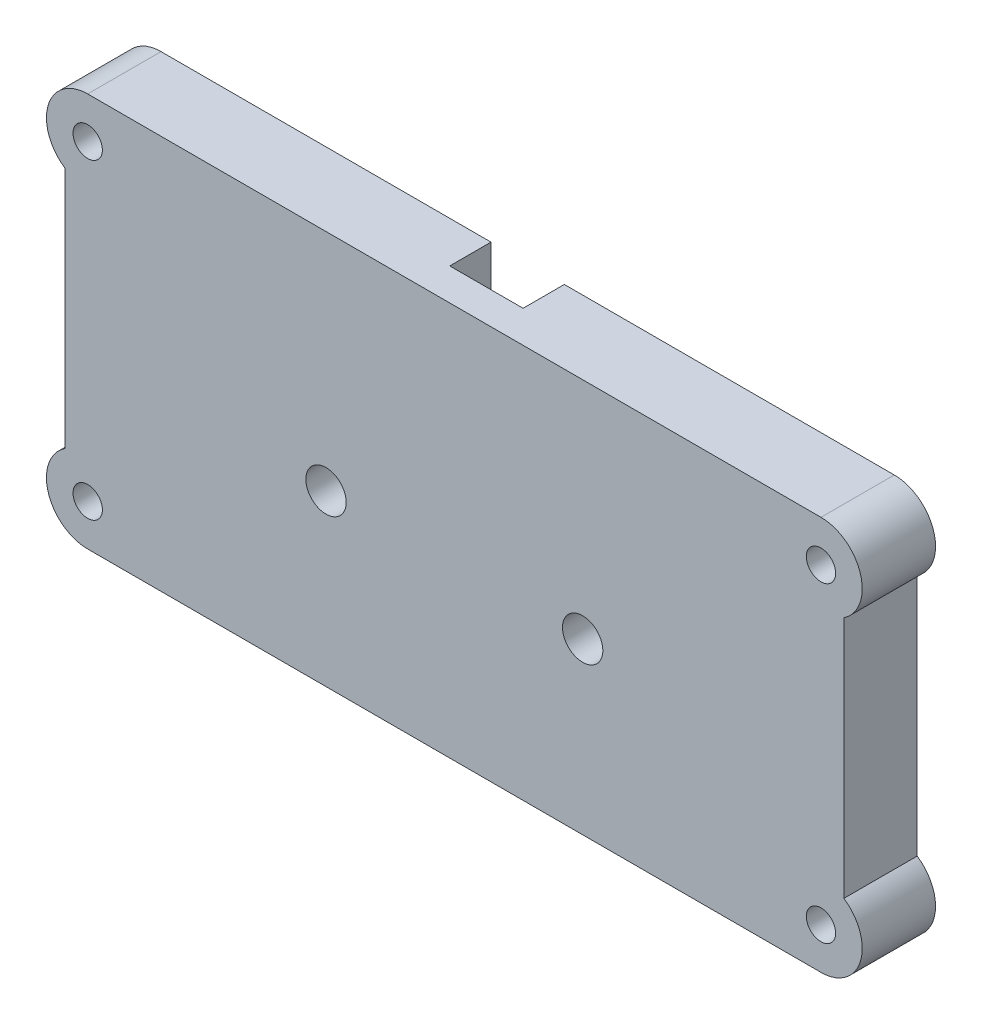
SolidWorks part; units mm, degrees
ref_plane "Front Plane" through (0, 0, 0) normal (0, 0, 1) x (1, 0, 0)
ref_plane "Top Plane" through (0, 0, 0) normal (0, 1, 0) x (1, 0, 0)
ref_plane "Right Plane" through (0, 0, 0) normal (1, 0, 0) x (0, 0, -1)
sketch "Sketch1" plane through (0, 0, 0) normal (0, 0, 1) x (1, 0, 0)
  line L0 (0, 62.8997) -> (0, -49.5687) construction
  line L5 (-81.1125, 0) -> (72.4755, 0) construction
  line L6 (-42.5, -13.2583) -> (-42.5, 13.2583)
  line L8 (0, 0) -> (-15.8735, 15.8735) construction
  line L10 (42.5, -13.2583) -> (42.5, 13.2583)
  line L11 (-40, 21.5) -> (40, 21.5)
  line L12 (-40, -21.5) -> (40, -21.5)
  line L13 (-5.4899, 9.874) -> (-9.8288, 14.2128)
  line L14 (-14.2128, 9.8288) -> (-9.874, 5.4899)
  line L15 (14.2128, 9.8288) -> (9.874, 5.4899)
  line L16 (5.4899, 9.874) -> (9.8288, 14.2128)
  line L17 (14.2128, -9.8288) -> (9.874, -5.4899)
  line L18 (5.4899, -9.874) -> (9.8288, -14.2128)
  line L19 (-5.4899, -9.874) -> (-9.8288, -14.2128)
  line L20 (-14.2128, -9.8288) -> (-9.874, -5.4899)
  line L22 (-7.1, -3.85) -> (7.1, -3.85)
  line L23 (-7.1, -3.85) -> (-7.1, 3.85)
  line L24 (-7.1, 3.85) -> (7.1, 3.85) construction
  line L25 (7.1, -3.85) -> (7.1, 3.85)
  line L26 (-7.1, -3.85) -> (7.1, 3.85) construction
  line L27 (-7.1, 3.85) -> (7.1, -3.85) construction
  line L28 (-7.1, 3.85) -> (7.1, 3.85) construction
  line L29 (-7.1, 3.85) -> (-7.1, 7.6)
  line L30 (-7.1, 7.6) -> (7.1, 7.6)
  line L31 (7.1, 3.85) -> (7.1, 7.6)
  line L32 (-4, 21.5) -> (4, 21.5)
  line L33 (-4, 21.5) -> (-4, 7.6)
  line L34 (-4, 7.6) -> (4, 7.6)
  line L35 (4, 21.5) -> (4, 7.6)
  arc A1 (-40, 21.5) -> (-42.5, 13.2583) centre (-40, 17) ccw
  arc A2 (-40, -21.5) -> (-42.5, -13.2583) centre (-40, -17) cw
  arc A3 (40, 21.5) -> (42.5, 13.2583) centre (40, 17) cw
  arc A4 (40, -21.5) -> (42.5, -13.2583) centre (40, -17) ccw
  circle A5 centre (0, 0) radius 17 construction
  arc A6 (-9.8288, 14.2128) -> (-14.2128, 9.8288) centre (-12.0208, 12.0208) ccw
  arc A7 (9.8288, 14.2128) -> (14.2128, 9.8288) centre (12.0208, 12.0208) cw
  arc A8 (-9.8288, -14.2128) -> (-14.2128, -9.8288) centre (-12.0208, -12.0208) cw
  arc A9 (9.8288, -14.2128) -> (14.2128, -9.8288) centre (12.0208, -12.0208) ccw
  arc A10 (-5.4899, 9.874) -> (5.4899, 9.874) centre (0, 15.364) ccw
  arc A11 (-5.4899, -9.874) -> (5.4899, -9.874) centre (0, -15.364) cw
  arc A12 (9.874, 5.4899) -> (9.874, -5.4899) centre (15.364, 0) ccw
  arc A13 (-9.874, 5.4899) -> (-9.874, -5.4899) centre (-15.364, 0) cw
  circle A14 centre (-40, 17) radius 1.6
  circle A15 centre (40, 17) radius 1.6
  circle A16 centre (-40, -17) radius 1.6
  circle A17 centre (40, -17) radius 1.6
  point P17 (-42.5, 0)
  point P23 (42.5, 0)
  dimension "D1" = 9
  dimension "D5" = 34
  dimension "D6" = 45
  dimension "D8" = 15.2
  dimension "D9" = 3.2
  dimension "D10" = 14.2
  dimension "D2" = 34
  dimension "D3" = 2.5
  dimension "D4" = 80
  dimension "D7" = 6.2
  dimension "D11" = 7.7
  dimension "D12" = 8
extrude "Boss-Extrude1" add sketch "Sketch1" along normal blind 8 contours L12 A4 L10 A3 L11 A1 L6 A2 A13 L14 A6 L13 A10 L16 A7 L15 A12 L17 A9 L18 A11 L19 A8 L20 | L22 L25 L24 L23 | L23 A13 L20 A8 L19 A11 L18 A9 L17 A12 L25 L22 | L14 A13 L23 L24 L25 A12 L15 A7 L16 A10 L13 A6 | L33 L32 L35 L34 region at (-41.5116, 0, 0) region at (-4.4277, 8.1549, 0) region at (0, 1.875, 0)
extrude "Cut-Extrude4" cut sketch "Sketch1<7>" along normal blind 1.7 contours L13 A6 L14 A13 L20 A8 L19 A11 L18 A9 L17 A12 L15 A7 L16 A10
sketch "Sketch1<7>" plane through (0, 0, 0) normal (0, 0, 1) x (1, 0, 0) same geometry as "Sketch1"
extrude "Cut-Extrude5" cut sketch "Sketch1<8>" along normal blind 7.4 contours L22 L25 L31 L30 L29 L23
sketch "Sketch1<8>" plane through (0, 0, 0) normal (0, 0, 1) x (1, 0, 0) same geometry as "Sketch1"
extrude "Cut-Extrude6" cut sketch "Sketch1<9>" along normal blind 4.5 contours L33 L34 L35 L32
sketch "Sketch1<9>" plane through (0, 0, 0) normal (0, 0, 1) x (1, 0, 0) same geometry as "Sketch1"
sketch "Sketch2" plane through (0, 0, 8) normal (0, 0, 1) x (1, 0, 0)
  line L0 (0, 9.8235) -> (0, -9.9073) construction
  line L1 (-20, 8) -> (20, 8) construction
  line L2 (-20, 8) -> (-20, -10) construction
  line L3 (-20, -10) -> (20, -10) construction
  line L4 (20, 8) -> (20, -10) construction
  line L5 (-21.3685, 0) -> (19.1836, 0) construction
  circle A0 centre (-14, -3) radius 2.2
  circle A1 centre (14, -3) radius 2.2
  circle A2 centre (0, -0.0419) radius 4 construction
  point P0 (0, 0)
  point P16 (0, 0)
  dimension "D3" = 4.4
  dimension "D4" = 28
  dimension "D5" = 3
  dimension "D7" = 8
  dimension "D1" = 40
  dimension "D2" = 8
  dimension "D6" = 20
  dimension "D8" = 10
extrude "Cut-Extrude11" cut sketch "Sketch2" against normal blind 6 contours A1 | A0
